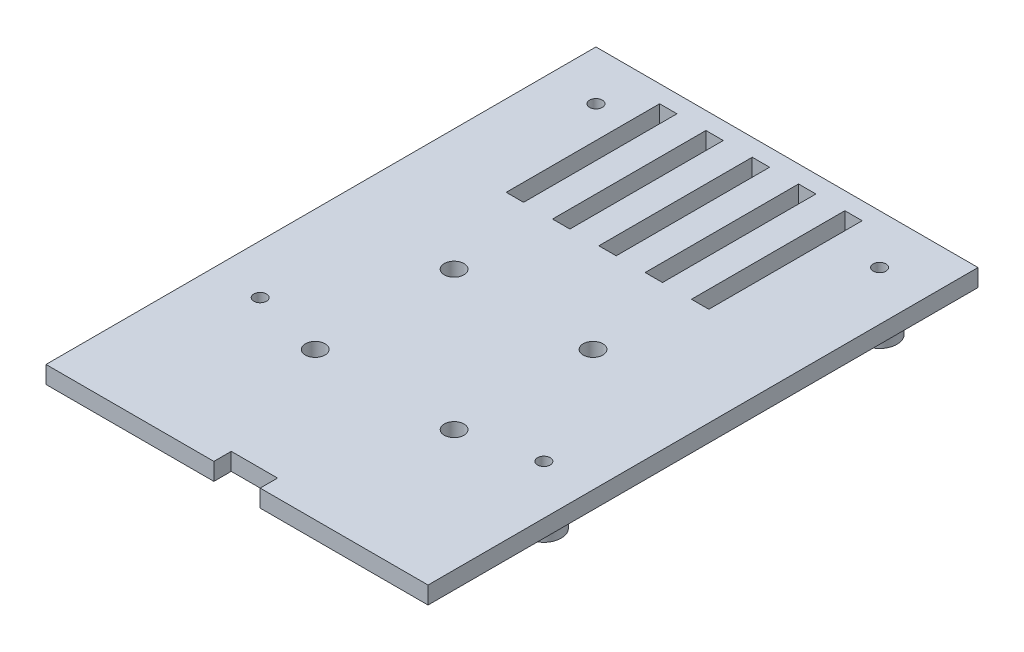
SolidWorks part; units mm, degrees
ref_plane "Front Plane" through (0, 0, 0) normal (0, 0, 1) x (1, 0, 0)
ref_plane "Top Plane" through (0, 0, 0) normal (0, 1, 0) x (1, 0, 0)
ref_plane "Right Plane" through (0, 0, 0) normal (1, 0, 0) x (0, 0, -1)
sketch "Sketch1" plane through (0, 0, 0) normal (0, 1, 0) x (1, 0, 0)
  line L1 (-131, 57.5) -> (-65, 57.5)
  line L2 (-131, 57.5) -> (-131, -37.5)
  line L3 (-131, -37.5) -> (-65, -37.5)
  line L4 (-65, 57.5) -> (-65, -37.5)
extrude "Cradle Base" add sketch "Sketch1" against normal blind 3
sketch "Sketch2" plane through (0, 0, 0) normal (0, 1, 0) x (1, 0, 0)
  circle A0 centre (-122.5, 49) radius 3
  circle A1 centre (-122.5, -9) radius 3
  circle A2 centre (-73.5, 49) radius 3
  circle A3 centre (-73.5, -9) radius 3
extrude "Standoffs" add sketch "Sketch2" against normal blind 10
sketch "Sketch3" plane through (0, 0, 0) normal (0, 1, 0) x (1, 0, 0)
  circle A0 centre (-122.5, 49) radius 1.1
  circle A1 centre (-122.5, -9) radius 1.1
  circle A2 centre (-73.5, 49) radius 1.1
  circle A3 centre (-73.5, -9) radius 1.1
  circle A4 centre (-110, -12) radius 1.7
  circle A5 centre (-110, 12) radius 1.7
  circle A6 centre (-86, -12) radius 1.7
  circle A7 centre (-86, 12) radius 1.7
extrude "Pilot and Bolt Holes" cut sketch "Sketch3" against normal through all and the other way through all
sketch "Sketch4" plane through (0, 0, 0) normal (0, 1, 0) x (1, 0, 0)
  line L1 (-85, 54.5) -> (-82, 54.5)
  line L2 (-85, 54.5) -> (-85, 28)
  line L3 (-85, 28) -> (-82, 28)
  line L4 (-82, 54.5) -> (-82, 28)
  line L6 (-93, 54.5) -> (-90, 54.5)
  line L7 (-93, 54.5) -> (-93, 28)
  line L8 (-93, 28) -> (-90, 28)
  line L9 (-90, 54.5) -> (-90, 28)
  line L11 (-101, 54.5) -> (-98, 54.5)
  line L12 (-101, 54.5) -> (-101, 28)
  line L13 (-101, 28) -> (-98, 28)
  line L14 (-98, 54.5) -> (-98, 28)
  line L16 (-109, 54.5) -> (-106, 54.5)
  line L17 (-109, 54.5) -> (-109, 28)
  line L18 (-109, 28) -> (-106, 28)
  line L19 (-106, 54.5) -> (-106, 28)
  line L21 (-117, 54.5) -> (-114, 54.5)
  line L22 (-117, 54.5) -> (-117, 28)
  line L23 (-117, 28) -> (-114, 28)
  line L24 (-114, 54.5) -> (-114, 28)
extrude "Vent Slots" cut sketch "Sketch4" against normal through all and the other way through all
sketch "Sketch5" plane through (0, 0, 0) normal (0, 1, 0) x (1, 0, 0)
  line L1 (-102, -34.5) -> (-94, -34.5)
  line L2 (-102, -34.5) -> (-102, -38.5)
  line L3 (-102, -38.5) -> (-94, -38.5)
  line L4 (-94, -34.5) -> (-94, -38.5)
extrude "USB End Notch" cut sketch "Sketch5" against normal through all and the other way through all
equation "\"BaseT\" = 3.0"
equation "\"StandH\" = 7.0"
equation "\"StandD\" = 6.0"
equation "\"PilotD\" = 2.2"
equation "\"BoltD\" = 3.4"
equation "\"PiCX\" = -98.0"
equation "\"PiCZ\" = -20.0"
equation "\"HoleL\" = 58.0"
equation "\"HoleW\" = 49.0"
